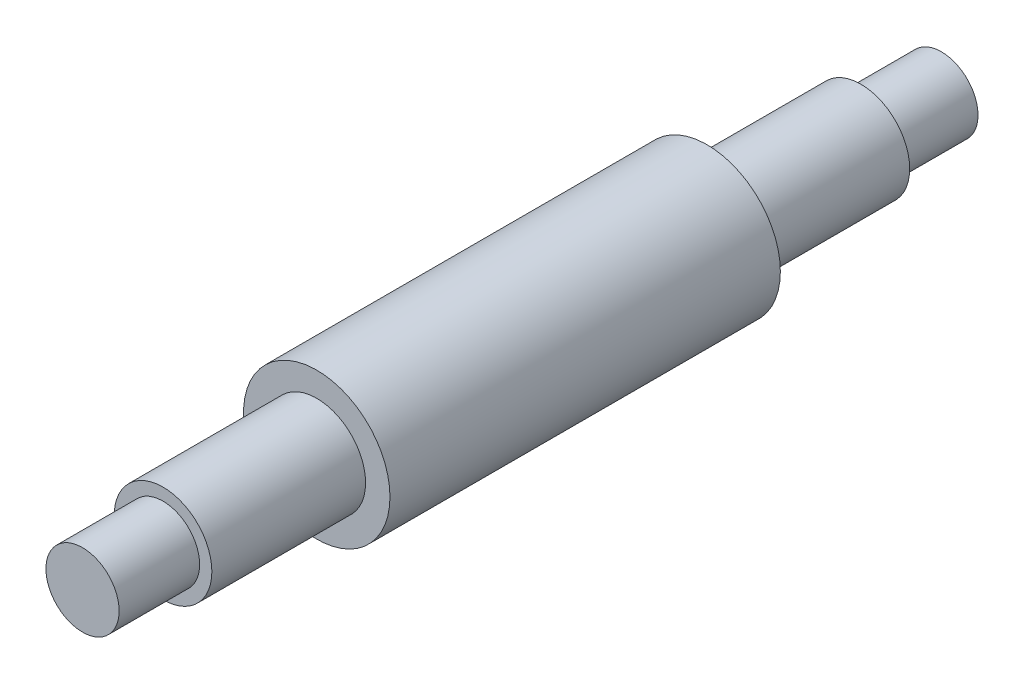
SolidWorks part; units mm, degrees
note: The reader was unsure of these and kept them because the rebuilt part matched: shared geometry of "Esquisse1<10>", "Esquisse1<7>", "Esquisse1<8>", "Esquisse1<11>".
ref_plane "Plan de face" through (0, 0, 0) normal (0, 0, 1) x (1, 0, 0)
ref_plane "Plan de dessus" through (0, 0, 0) normal (0, 1, 0) x (1, 0, 0)
ref_plane "Plan de droite" through (0, 0, 0) normal (1, 0, 0) x (0, 0, -1)
sketch "Esquisse1" plane through (0, 0, 0) normal (0, 0, 1) x (1, 0, 0)
  line L0 (-48.5255, 0) -> (60.6197, 0) construction
  line L1 (0, 41.1471) -> (0, -40.7888) construction
  circle A0 centre (0, 0) radius 15
  circle A1 centre (0, 0) radius 25
  circle A2 centre (0, 0) radius 20 construction
  circle A3 centre (0, 20) radius 4
  circle A4 centre (0, 20) radius 2.5
  circle A15 centre (0, 0) radius 10
  circle A16 centre (17.3205, 10) radius 4
  circle A17 centre (17.3205, 10) radius 2.5
  circle A18 centre (17.3205, -10) radius 4
  circle A19 centre (17.3205, -10) radius 2.5
  circle A20 centre (0, -20) radius 4
  circle A21 centre (0, -20) radius 2.5
  circle A22 centre (-17.3205, -10) radius 4
  circle A23 centre (-17.3205, -10) radius 2.5
  circle A24 centre (-17.3205, 10) radius 4
  circle A25 centre (-17.3205, 10) radius 2.5
  circle A26 centre (0, 0) radius 7.5
  circle A27 centre (0, 0) radius 2.5
  point P29 (0, 0)
  point P30 (-8.6942, -5.0196)
  dimension "D1" = 30
  dimension "D2" = 40
  dimension "D3" = 50
  dimension "D4" = 8
  dimension "D5" = 5
  dimension "D6" = 20
  dimension "D8" = 15
  dimension "D9" = 5
  dimension "D7" = 6
extrude "Boss.-Extru.1" add sketch "Esquisse1" along normal mid plane 80 contours A0
extrude "Boss.-Extru.5" add sketch "Esquisse1<10>" along normal blind 31.5 from offset 40 contours A15
sketch "Esquisse1<10>" plane through (0, 0, 0) normal (0, 0, 1) x (1, 0, 0) same geometry as "Esquisse1"
extrude "Boss.-Extru.3" add sketch "Esquisse1<7>" along normal blind 16.5 from offset 71.5 separate body contours A26
sketch "Esquisse1<7>" plane through (0, 0, 0) normal (0, 0, 1) x (1, 0, 0) same geometry as "Esquisse1"
extrude "Boss.-Extru.4" add sketch "Esquisse1<8>" against normal blind 16.5 from offset 71.5 contours A26 offset against normal yes
sketch "Esquisse1<8>" plane through (0, 0, 0) normal (0, 0, 1) x (1, 0, 0) same geometry as "Esquisse1"
extrude "Boss.-Extru.6" add sketch "Esquisse1<11>" against normal blind 31.5 from offset 40 contours A15 offset against normal yes
sketch "Esquisse1<11>" plane through (0, 0, 0) normal (0, 0, 1) x (1, 0, 0) same geometry as "Esquisse1"
sketch "Esquisse2" plane through (0, 0, 40) normal (0, 0, 1) x (1, 0, 0)
  circle A1 centre (0, 0) radius 15
  circle A2 centre (0, 0) radius 15
  dimension "D1" = 0
curve "Hélice/Spirale1" pitch 160 height 80 turns 0.5
